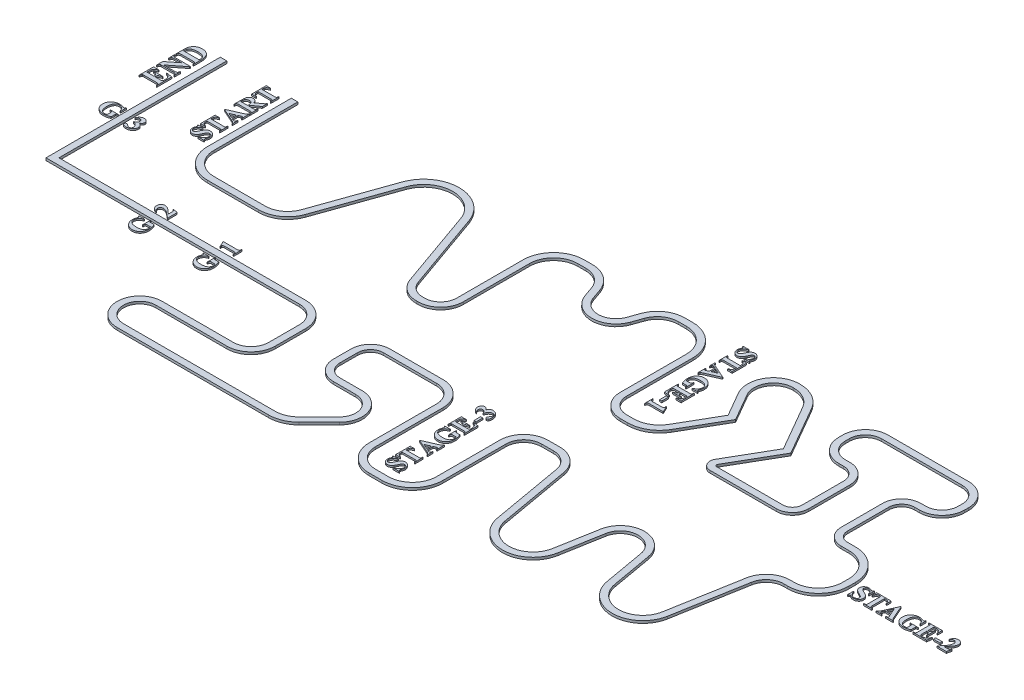
SolidWorks part; units mm, degrees
ref_plane "Front Plane" through (0, 0, 0) normal (0, 0, 1) x (1, 0, 0)
ref_plane "Top Plane" through (0, 0, 0) normal (0, 1, 0) x (1, 0, 0)
ref_plane "Right Plane" through (0, 0, 0) normal (1, 0, 0) x (0, 0, -1)
sketch "Sketch1" plane through (0, 0, 0) normal (0, 1, 0) x (1, 0, 0)
  line L0 (-2000, 850) -> (-2000, 330)
  line L1 (-1820, 150) -> (-1502.2309, 150)
  line L2 (-1332.5468, 269.9393) -> (-1169.6842, 730.0607)
  line L9 (-1000, 1000) -> (-1000, 0) construction
  line L10 (-658.0192, 243.2861) -> (-830.3158, 730.0607)
  line L11 (-52.8541, 763.3772) -> (-30.4035, 699.9494)
  line L14 (-2000, 590) -> (2045.211, 475.1392) construction
  line L30 (1417.787, -380) -> (1417.787, -1000) construction
  line L56 (1565.5082, -503.9528) -> (1609.9593, -756.0472)
  line L58 (1983.3548, -313.9528) -> (1905.4016, -756.0472)
  line L59 (-140.3476, -710.7107) -> (-265.7029, -836.066)
  line L60 (1805.211, 250) -> (1805.211, 506.1678)
  line L62 (-2000, 0) -> (2000, 0) construction
  line L64 (-2000, 1000) -> (2000, 1000) construction
  line L65 (-2000, 1000) -> (-2000, -1000) construction
  line L66 (704.4982, -190) -> (630.3631, -190)
  line L67 (480.3631, -340) -> (480.3631, -730)
  line L68 (330.3631, -880) -> (250.3631, -880)
  line L69 (130.3631, -760) -> (130.3631, -340)
  line L70 (-19.6369, -190) -> (-349.6369, -190)
  line L71 (-469.6369, -310) -> (-469.6369, -420)
  line L72 (-349.6369, -540) -> (-211.0583, -540)
  line L74 (-371.7689, -880) -> (-1309.6369, -880)
  line L75 (-1309.6369, -880) -> (-1309.6369, -680) construction
  line L76 (-1309.6369, -680) -> (-869.6369, -680)
  line L77 (-719.6369, -530) -> (-719.6369, -340)
  line L78 (-869.6369, -190) -> (-2400, -190)
  line L79 (-2000, -1000) -> (2000, -1000) construction
  line L80 (2000, 1000) -> (2000, -1000) construction
  line L81 (-2000, 1000) -> (2000, -1000) construction
  line L82 (-2000, -1000) -> (2000, 1000) construction
  line L83 (-1200, 1000) -> (-1200, -1000) construction
  line L84 (-400, 1000) -> (-400, -1000) construction
  line L85 (400, 1000) -> (400, -1000) construction
  line L86 (1200, 1000) -> (1200, -1000) construction
  line L87 (-526.0426, 150) -> (-515, 150)
  line L88 (-375, 290) -> (-375, 700)
  line L89 (-225, 850) -> (-175.4038, 850)
  line L91 (597, 700) -> (597, 290)
  line L92 (111, 1000) -> (111, 600) construction
  line L93 (737, 150) -> (781.5299, 150)
  line L94 (954.735, 250) -> (1100.211, 501.9718)
  line L95 (1100.211, 501.9718) -> (1002.5256, 671.1678)
  line L96 (1106.4486, 851.1678) -> (1112, 851.1678)
  line L97 (1241.9038, 776.1678) -> (1405.211, 493.3115)
  line L98 (1405.211, 493.3115) -> (1250.3013, 225)
  line L99 (1293.6025, 150) -> (1705.211, 150)
  line L100 (1685.211, 626.1678) -> (1655.211, 626.1678)
  line L101 (1555.211, 726.1678) -> (1555.211, 751.1678)
  line L102 (1655.211, 851.1678) -> (2155.211, 851.1678)
  line L103 (2255.211, 751.1678) -> (2255.211, 726.1678)
  line L104 (2155.211, 626.1678) -> (2125.211, 626.1678)
  line L105 (2005.211, 506.1678) -> (2005.211, 250)
  line L106 (2105.211, 150) -> (2155.211, 150)
  line L107 (2305.211, 0) -> (2305.211, -40)
  line L108 (2155.211, -190) -> (2131.0759, -190)
  line L109 (852.2193, -313.9528) -> (930.1725, -756.0472)
  line L110 (1270.0659, -503.9528) -> (1225.6148, -756.0472)
  line L111 (-1960, 850) -> (-1960, 330)
  line L112 (-1820, 190) -> (-1502.2309, 190)
  line L113 (-1370.2544, 283.2861) -> (-1207.3917, 743.4075)
  line L114 (-620.3116, 256.6329) -> (-792.6083, 743.4075)
  line L115 (-526.0426, 190) -> (-515, 190)
  line L116 (-415, 290) -> (-415, 700)
  line L117 (-225, 890) -> (-175.4038, 890)
  line L118 (-15.1465, 776.724) -> (7.3041, 713.2962)
  line L121 (637, 700) -> (637, 290)
  line L122 (737, 190) -> (781.5299, 190)
  line L123 (920.094, 270) -> (1054.023, 501.9718)
  line L124 (1054.023, 501.9718) -> (967.8846, 651.1678)
  line L125 (1106.4486, 891.1678) -> (1112, 891.1678)
  line L126 (1276.5448, 796.1678) -> (1451.399, 493.3115)
  line L127 (1451.399, 493.3115) -> (1284.9423, 205)
  line L128 (1293.6025, 190) -> (1705.211, 190)
  line L129 (1765.211, 250) -> (1765.211, 506.1678)
  line L130 (1685.211, 586.1678) -> (1655.211, 586.1678)
  line L131 (1515.211, 726.1678) -> (1515.211, 751.1678)
  line L132 (1655.211, 891.1678) -> (2155.211, 891.1678)
  line L133 (2295.211, 751.1678) -> (2295.211, 726.1678)
  line L134 (2155.211, 586.1678) -> (2125.211, 586.1678)
  line L135 (2045.211, 506.1678) -> (2045.211, 250)
  line L136 (2105.211, 190) -> (2155.211, 190)
  line L137 (2345.211, 0) -> (2345.211, -40)
  line L138 (2155.211, -230) -> (2131.0759, -230)
  line L139 (2022.7471, -320.8987) -> (1944.7939, -762.9932)
  line L140 (1526.1159, -510.8987) -> (1570.567, -762.9932)
  line L141 (1309.4582, -510.8987) -> (1265.0071, -762.9932)
  line L142 (812.827, -320.8987) -> (890.7802, -762.9932)
  line L143 (704.4982, -230) -> (630.3631, -230)
  line L144 (520.3631, -340) -> (520.3631, -730)
  line L145 (330.3631, -920) -> (250.3631, -920)
  line L146 (90.3631, -760) -> (90.3631, -340)
  line L147 (-19.6369, -230) -> (-349.6369, -230)
  line L148 (-429.6369, -310) -> (-429.6369, -420)
  line L149 (-349.6369, -500) -> (-211.0583, -500)
  line L150 (-112.0633, -738.9949) -> (-237.4186, -864.3503)
  line L151 (-371.7689, -920) -> (-1309.6369, -920)
  line L152 (-1309.6369, -640) -> (-869.6369, -640)
  line L153 (-759.6369, -530) -> (-759.6369, -340)
  line L154 (-869.6369, -230) -> (-2440, -230)
  line L155 (-2000, 850) -> (-1960, 850)
  line L157 (237.1465, 776.724) -> (214.6959, 713.2962)
  line L158 (274.8541, 763.3772) -> (252.4035, 699.9494)
  line L159 (447, 890) -> (397.4038, 890)
  line L160 (447, 850) -> (397.4038, 850)
  line L161 (637, 689.8201) -> (637, 290) construction
  line L162 (362.0486, 850) -> (492.3602, 850) construction
  line L163 (362.0486, 890) -> (488.8251, 890) construction
  line L164 (252.4035, 699.9494) -> (263.3909, 766.33) construction
  line L165 (213.5623, 710.2385) -> (223.9279, 772.862) construction
  line L166 (-2400, 850) -> (-2400, -190)
  line L167 (-869.6369, -190) -> (-2000, -190) construction
  line L168 (-2440, 850) -> (-2440, -230)
  line L169 (-2440, -190) -> (-2440, -230) construction
  line L170 (-869.6369, -230) -> (-2000, -230) construction
  line L171 (-2440, 850) -> (-2440, -190) construction
  line L172 (-2440, 850) -> (-2400, 850)
  arc A38 (1905.4016, -756.0472) -> (1609.9593, -756.0472) centre (1757.6804, -730) cw
  arc A39 (1565.5082, -503.9528) -> (1270.0659, -503.9528) centre (1417.787, -530) ccw
  arc A45 (-1169.6842, 730.0607) -> (-830.3158, 730.0607) centre (-1000, 670) cw
  arc A48 (-375, 700) -> (-225, 850) centre (-225, 700) cw
  arc A49 (-30.4035, 699.9494) -> (252.4035, 699.9494) centre (111, 750) ccw
  arc A50 (-175.4038, 850) -> (-52.8541, 763.3772) centre (-175.4038, 720) cw
  arc A52 (930.1725, -756.0472) -> (1225.6148, -756.0472) centre (1077.8937, -730) ccw
  arc A53 (781.5299, 150) -> (954.735, 250) centre (781.5299, 350) ccw
  arc A54 (-2000, 330) -> (-1820, 150) centre (-1820, 330) ccw
  arc A55 (-1502.2309, 150) -> (-1332.5468, 269.9393) centre (-1502.2309, 330) ccw
  arc A56 (597, 290) -> (737, 150) centre (737, 290) ccw
  arc A57 (-515, 150) -> (-375, 290) centre (-515, 290) ccw
  arc A58 (-658.0192, 243.2861) -> (-526.0426, 150) centre (-526.0426, 290) ccw
  arc A59 (1002.5256, 671.1678) -> (1106.4486, 851.1678) centre (1106.4486, 731.1678) cw
  arc A60 (1112, 851.1678) -> (1241.9038, 776.1678) centre (1112, 701.1678) cw
  arc A61 (1250.3013, 225) -> (1293.6025, 150) centre (1293.6025, 200) ccw
  arc A62 (2255.211, 726.1678) -> (2155.211, 626.1678) centre (2155.211, 726.1678) cw
  arc A63 (2155.211, 851.1678) -> (2255.211, 751.1678) centre (2155.211, 751.1678) cw
  arc A64 (1555.211, 751.1678) -> (1655.211, 851.1678) centre (1655.211, 751.1678) cw
  arc A65 (1655.211, 626.1678) -> (1555.211, 726.1678) centre (1655.211, 726.1678) cw
  arc A66 (2005.211, 250) -> (2105.211, 150) centre (2105.211, 250) ccw
  arc A67 (1705.211, 150) -> (1805.211, 250) centre (1705.211, 250) ccw
  arc A68 (480.3631, -730) -> (330.3631, -880) centre (330.3631, -730) cw
  arc A69 (630.3631, -190) -> (480.3631, -340) centre (630.3631, -340) ccw
  arc A70 (852.2193, -313.9528) -> (704.4982, -190) centre (704.4982, -340) ccw
  arc A71 (2131.0759, -190) -> (1983.3548, -313.9528) centre (2131.0759, -340) ccw
  arc A72 (2305.211, -40) -> (2155.211, -190) centre (2155.211, -40) cw
  arc A73 (2155.211, 150) -> (2305.211, 0) centre (2155.211, 0) cw
  arc A74 (250.3631, -880) -> (130.3631, -760) centre (250.3631, -760) cw
  arc A75 (130.3631, -340) -> (-19.6369, -190) centre (-19.6369, -340) ccw
  arc A76 (-469.6369, -420) -> (-349.6369, -540) centre (-349.6369, -420) ccw
  arc A77 (-349.6369, -190) -> (-469.6369, -310) centre (-349.6369, -310) ccw
  arc A78 (-211.0583, -540) -> (-140.3476, -710.7107) centre (-211.0583, -640) cw
  arc A79 (-719.6369, -340) -> (-869.6369, -190) centre (-869.6369, -340) ccw
  arc A80 (-869.6369, -680) -> (-719.6369, -530) centre (-869.6369, -530) ccw
  arc A81 (-265.7029, -836.066) -> (-371.7689, -880) centre (-371.7689, -730) cw
  arc A82 (-1309.6369, -880) -> (-1309.6369, -680) centre (-1309.6369, -780) cw
  arc A83 (2125.211, 626.1678) -> (2005.211, 506.1678) centre (2125.211, 506.1678) ccw
  arc A84 (1805.211, 506.1678) -> (1685.211, 626.1678) centre (1685.211, 506.1678) ccw
  arc A85 (-1960, 330) -> (-1820, 190) centre (-1820, 330) ccw
  arc A86 (-1502.2309, 190) -> (-1370.2544, 283.2861) centre (-1502.2309, 330) ccw
  arc A87 (-1207.3917, 743.4075) -> (-792.6083, 743.4075) centre (-1000, 670) cw
  arc A88 (-620.3116, 256.6329) -> (-526.0426, 190) centre (-526.0426, 290) ccw
  arc A89 (-515, 190) -> (-415, 290) centre (-515, 290) ccw
  arc A90 (-415, 700) -> (-225, 890) centre (-225, 700) cw
  arc A91 (-175.4038, 890) -> (-15.1465, 776.724) centre (-175.4038, 720) cw
  arc A92 (7.3041, 713.2962) -> (214.6959, 713.2962) centre (111, 750) ccw
  arc A95 (637, 290) -> (737, 190) centre (737, 290) ccw
  arc A96 (781.5299, 190) -> (920.094, 270) centre (781.5299, 350) ccw
  arc A97 (967.8846, 651.1678) -> (1106.4486, 891.1678) centre (1106.4486, 731.1678) cw
  arc A98 (1112, 891.1678) -> (1276.5448, 796.1678) centre (1112, 701.1678) cw
  arc A99 (1284.9423, 205) -> (1293.6025, 190) centre (1293.6025, 200) ccw
  arc A100 (1705.211, 190) -> (1765.211, 250) centre (1705.211, 250) ccw
  arc A101 (1765.211, 506.1678) -> (1685.211, 586.1678) centre (1685.211, 506.1678) ccw
  arc A102 (1655.211, 586.1678) -> (1515.211, 726.1678) centre (1655.211, 726.1678) cw
  arc A103 (1515.211, 751.1678) -> (1655.211, 891.1678) centre (1655.211, 751.1678) cw
  arc A104 (2155.211, 891.1678) -> (2295.211, 751.1678) centre (2155.211, 751.1678) cw
  arc A105 (2295.211, 726.1678) -> (2155.211, 586.1678) centre (2155.211, 726.1678) cw
  arc A106 (2125.211, 586.1678) -> (2045.211, 506.1678) centre (2125.211, 506.1678) ccw
  arc A107 (2045.211, 250) -> (2105.211, 190) centre (2105.211, 250) ccw
  arc A108 (2155.211, 190) -> (2345.211, 0) centre (2155.211, 0) cw
  arc A109 (2345.211, -40) -> (2155.211, -230) centre (2155.211, -40) cw
  arc A110 (2131.0759, -230) -> (2022.7471, -320.8987) centre (2131.0759, -340) ccw
  arc A111 (1944.7939, -762.9932) -> (1570.567, -762.9932) centre (1757.6804, -730) cw
  arc A112 (1526.1159, -510.8987) -> (1309.4582, -510.8987) centre (1417.787, -530) ccw
  arc A113 (890.7802, -762.9932) -> (1265.0071, -762.9932) centre (1077.8937, -730) ccw
  arc A114 (812.827, -320.8987) -> (704.4982, -230) centre (704.4982, -340) ccw
  arc A115 (630.3631, -230) -> (520.3631, -340) centre (630.3631, -340) ccw
  arc A116 (520.3631, -730) -> (330.3631, -920) centre (330.3631, -730) cw
  arc A117 (250.3631, -920) -> (90.3631, -760) centre (250.3631, -760) cw
  arc A118 (90.3631, -340) -> (-19.6369, -230) centre (-19.6369, -340) ccw
  arc A119 (-349.6369, -230) -> (-429.6369, -310) centre (-349.6369, -310) ccw
  arc A120 (-429.6369, -420) -> (-349.6369, -500) centre (-349.6369, -420) ccw
  arc A121 (-211.0583, -500) -> (-112.0633, -738.9949) centre (-211.0583, -640) cw
  arc A122 (-237.4186, -864.3503) -> (-371.7689, -920) centre (-371.7689, -730) cw
  arc A123 (-1309.6369, -920) -> (-1309.6369, -640) centre (-1309.6369, -780) cw
  arc A124 (-869.6369, -640) -> (-759.6369, -530) centre (-869.6369, -530) ccw
  arc A125 (-759.6369, -340) -> (-869.6369, -230) centre (-869.6369, -340) ccw
  arc A126 (397.4038, 850) -> (274.8541, 763.3772) centre (397.4038, 720) ccw
  arc A127 (397.4038, 890) -> (237.1465, 776.724) centre (397.4038, 720) ccw
  arc A128 (597, 700) -> (447, 850) centre (447, 700) ccw
  arc A129 (637, 700) -> (447, 890) centre (447, 700) ccw
  arc A130 (597, 700) -> (492.3602, 850) centre (511.4903, 751.8469) ccw construction
  arc A131 (637, 689.8201) -> (488.8251, 890) centre (511.4903, 751.8469) ccw construction
  arc A132 (362.0486, 850) -> (263.3909, 766.33) centre (362.0486, 750) ccw construction
  arc A133 (362.0486, 890) -> (223.9279, 772.862) centre (362.0486, 750) ccw construction
  arc A134 (7.3041, 713.2962) -> (213.5623, 710.2385) centre (111, 750) ccw construction
  point P14 (-375, 850)
  point P23 (-83.5147, 850)
  point P52 (897, 150)
  point P54 (4220.4062, -343.1918)
  point P58 (-2000, 150)
  point P61 (-1375, 150)
  point P64 (597, 150)
  point P67 (-375, 150)
  point P71 (-625, 150)
  point P73 (1757.6804, -880)
  point P76 (0, 0)
  point P87 (-1000, 850)
  point P95 (898.6025, 851.1678)
  point P97 (1077.8937, -880)
  point P99 (1198.6025, 851.1678)
  point P106 (2255.211, 851.1678)
  point P109 (1555.211, 851.1678)
  point P114 (2005.211, 150)
  point P117 (1805.211, 150)
  point P126 (830.3631, -190)
  point P129 (2005.211, -190)
  point P132 (2305.211, -190)
  point P135 (2305.211, 150)
  point P148 (130.3631, -190)
  point P151 (2432.0949, -360.4159)
  point P152 (-469.6369, -540)
  point P156 (480.3631, -190)
  point P157 (-469.6369, -190)
  point P161 (30.3631, -540)
  point P171 (-309.6369, -880)
  point P172 (4140.4062, -123.1918)
  point P173 (3698.8517, 0)
  point P174 (3778.8517, -80)
  point P176 (4220.4062, -123.1918)
  point P181 (1805.211, 626.1678)
  point P309 (0, 0)
  point P323 (0, 0)
  dimension "D4" = 2000
  dimension "D7" = 625
  dimension "D8" = 225
  dimension "D9" = 180
  dimension "D5" = 700
  dimension "D12" = 800
  dimension "D13" = 4
  dimension "D21" = 130
  dimension "D22" = 150
  dimension "D40" = 730
  dimension "D41" = 500
  dimension "D42" = 350
  dimension "D43" = 350
  dimension "D44" = 600
  dimension "D45" = 500
  dimension "D46" = 45
  dimension "D47" = 250
  dimension "D51" = 180
  dimension "D52" = 140
  dimension "D54" = 150
  dimension "D56" = 100
  dimension "D59" = 120
  dimension "D61" = 120
  dimension "D62" = 100
  dimension "D35" = 100
  dimension "D29" = 120
  dimension "D32" = 350
  dimension "D33" = 200
  dimension "D34" = 150
  dimension "D37" = 150
  dimension "D48" = 1000
  dimension "D49" = 200
  dimension "D53" = 120
  dimension "D55" = 50
  dimension "D57" = 100
  dimension "D58" = 150
  dimension "D30" = 150
  dimension "D11" = 200
  dimension "D14" = 250
  dimension "D15" = 800
  dimension "D17" = 475
  dimension "D6" = 180
  dimension "D19" = 150
  dimension "D20" = 400
  dimension "D25" = 344.5965
  dimension "D38" = 150
  dimension "D39" = 300
  dimension "D50" = 200
  dimension "D60" = 150
  dimension "D63" = 150
  dimension "D64" = 305
  dimension "D65" = 120
  dimension "D10" = 486
  dimension "D2" = 4000
  dimension "D16" = 150
  dimension "D18" = 1621.1678
  dimension "D23" = 250
  dimension "D24" = 40
  dimension "D26" = 300
  dimension "D27" = 300
  dimension "D31" = 700
  dimension "D36" = 340
  dimension "D28" = 120
  dimension "D66" = 40
  dimension "D67" = 4785.211
  dimension "D68" = 1080
extrude "Boss-Extrude1" add sketch "Sketch1" along normal blind 15
sketch "Sketch2" plane through (0, 0, 0) normal (0, 1, 0) x (1, 0, 0)
  line L0 (-2050, 850) -> (-2050, 350) construction
  line L1 (-2490, 850) -> (-2490, 350) construction
  line L2 (727, 190) -> (727, 1040) construction
  line L4 (477, 1040) -> (977, 1040) construction
  line L5 (2339.8051, -85) -> (3039.8051, -85) construction
  line L6 (-2000, 0) -> (2000, 0) construction
  line L7 (330.3631, -880) -> (330.3631, -130) construction
  line L9 (-1344.6369, 0) -> (-1344.6369, -400) construction
  line L11 (-1744.6369, 0) -> (-1744.6369, -400) construction
  line L12 (-2640, 190) -> (-2240, 190) construction
  line L13 (-2440, 850) -> (-2440, -230) construction
  line L14 (637, 290) -> (637, 700) construction
  arc A0 (2155.211, -230) -> (2345.211, -40) centre (2155.211, -40) ccw construction
  text T0 "START" font "Times New Roman" height 100
  text T1 "END" font "Times New Roman" height 110
  text T2 "STAGE-1" font "Times New Roman" height 100
  text T3 "STAGE-3" font "Times New Roman" height 100
  text T4 "STAGE-2" font "Times New Roman" height 100
  text T5 "G 1 " font "Times New Roman" height 100
  text T6 "G 2 " font "Times New Roman" height 100
  text T7 "G 3" font "Times New Roman" height 100
  point P17 (727, 1040)
  point P32 (-1344.6369, -200)
  point P35 (-2440, 190)
  point P45 (0, 0)
  dimension "D1" = 50
  dimension "D2" = 500
  dimension "D4" = 850
  dimension "D5" = 500
  dimension "D6" = 750
  dimension "D7" = 145
  dimension "D8" = 700
  dimension "D9" = 200
  dimension "D10" = 475
  dimension "D11" = 400
  dimension "D12" = 400
  dimension "D13" = 420
  dimension "D14" = 90
  dimension "D3" = 440
extrude "Boss-Extrude2" add sketch "Sketch2" along normal blind 10 separate body
